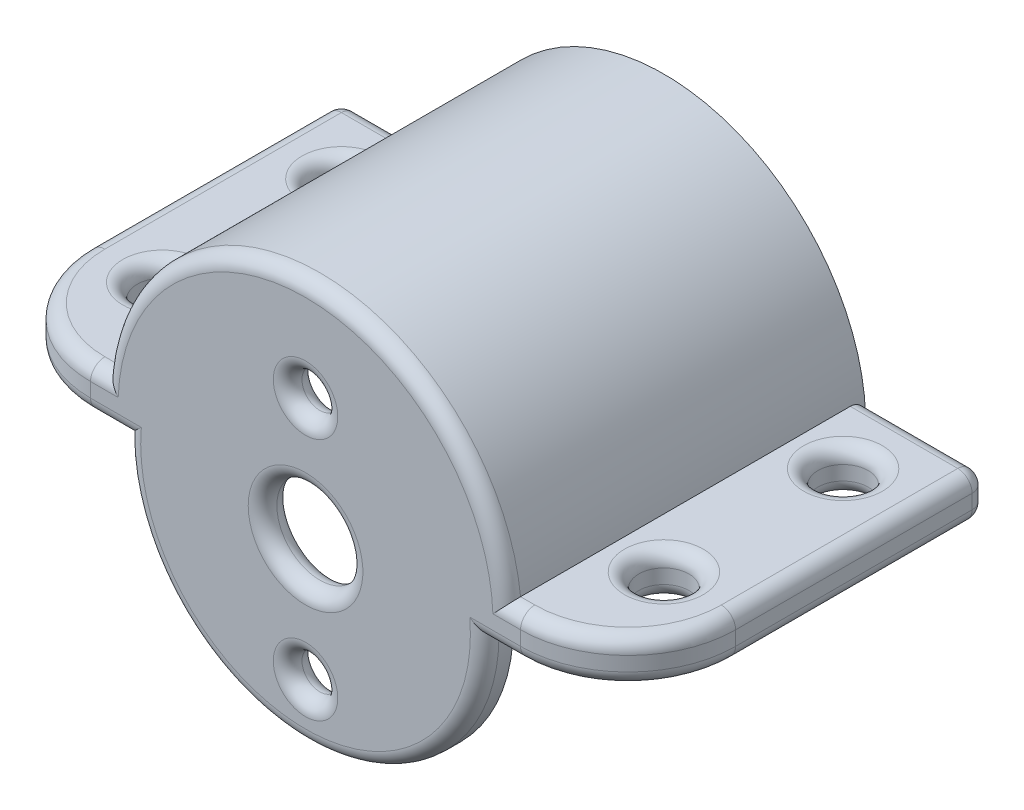
SolidWorks part; units mm, degrees
ref_plane "Front Plane" through (0, 0, 0) normal (0, 0, 1) x (1, 0, 0)
ref_plane "Top Plane" through (0, 0, 0) normal (0, 1, 0) x (1, 0, 0)
ref_plane "Right Plane" through (0, 0, 0) normal (1, 0, 0) x (0, 0, -1)
sketch "Sketch1" plane through (0, 0, 0) normal (0, 1, 0) x (1, 0, 0)
  line L1 (-22.5, 25) -> (-12.5, 25)
  line L2 (-22.5, 25) -> (-22.5, 0)
  line L3 (-22.5, 0) -> (-12.5, 0)
  line L4 (-12.5, 25) -> (-12.5, 0)
  line L5 (12.5, 25) -> (22.5, 25)
  line L6 (12.5, 25) -> (12.5, 0)
  line L7 (12.5, 0) -> (22.5, 0)
  line L8 (22.5, 25) -> (22.5, 0)
  circle A0 centre (-17.5, 20) radius 1.75
  circle A1 centre (-17.5, 7.5) radius 1.75
  circle A2 centre (17.5, 20) radius 1.75
  circle A3 centre (17.5, 7.5) radius 1.75
  point P22 (-17.5, 0)
  point P24 (17.5, 0)
  dimension "D5" = 3.5
  dimension "D1" = 25
  dimension "D2" = 12.5
  dimension "D3" = 10
  dimension "D4" = 25
  dimension "D6" = 7.5
  dimension "D7" = 5
extrude "Boss-Extrude1" add sketch "Sketch1" along normal blind 3
sketch "Sketch2" plane through (0, 0, 0) normal (0, 0, 1) x (1, 0, 0)
  line L0 (-22.5, 0) -> (-12.5, 0) construction
  line L1 (12.5, 0) -> (22.5, 0) construction
  line L2 (-14, 0) -> (-12.5, 0)
  line L3 (12.5, 0) -> (14, 0)
  arc A0 (-12.5, 0) -> (12.5, 0) centre (0, 0) cw
  arc A1 (-14, 0) -> (14, 0) centre (0, 1.5) cw
  dimension "D1" = 12.5
  dimension "D4" = 1.5
  dimension "D2" = 1.5
  dimension "D3" = 1.5
extrude "Boss-Extrude2" add sketch "Sketch2" against normal up to surface (25 mm away) up to face at (-17.5, 1.5, -25)
sketch "Sketch3" plane through (0, 0, 0) normal (0, 0, 1) x (1, 0, 0)
  arc A0 (12.5, 0) -> (-12.5, 0) centre (0, 0) ccw construction
  arc A1 (12.5, 0) -> (-12.5, 0) centre (0, 0) ccw
  circle A2 centre (0, 0) radius 12.5
  circle A3 centre (0, 8.5) radius 1.25
  circle A4 centre (0, -8.5) radius 1.25
  circle A5 centre (0, 0) radius 3
  arc M9 (-12.5, 0) -> (12.5, 0) centre (0, 0) cw
  dimension "D1" = 2.5
  dimension "D4" = 6
  dimension "D2" = 8.5
  dimension "D3" = 8.5
extrude "Boss-Extrude3" add sketch "Sketch3" against normal blind 2 contours A2 A4 A3 M9 region at (0, -12.1464, 0)
fillet "Fillet1" radius 7.5 2 edges at (-22.5, 1.5, 0) (22.5, 1.5, 0)
fillet "Fillet2" radius 1 30 edges at (22.5, 3, -16.25) (20.3033, 3, -2.1967) (22.5, 0, -16.25) (20.3033, 0, -2.1967) (-22.5, 0, -16.25) (-20.3033, 0, -2.1967) (-22.5, 3, -16.25) (-20.3033, 3, -2.1967) (1.25, 8.5, 0) (1.25, -8.5, 0) (3, 0, 0) (0, 15.5801, 0) (14.5, 3, 0) (13.75, 0, 0) (0, -12.5, 0) (-13.75, 0, 0) (-14.5, 3, 0) (-17.5, 0, -18.25) (-17.5, 3, -18.25) (-17.5, 0, -5.75) (-17.5, 3, -5.75) (17.5, 0, -18.25) (17.5, 3, -18.25) (17.5, 0, -5.75) (17.5, 3, -5.75) (1.25, -8.5, -2) (3, 0, -2) (1.25, 8.5, -2) (-12.5, 0, -13.5) (12.5, 0, -13.5)
fillet "Fillet3" radius 1 13 edges at (17.75, 3, -25) (22.2071, 2.7071, -25) (22.5, 1.5, -25) (22.2071, 0.2929, -25) (17.4815, 0, -25) (12.7825, 0.2672, -25) (-17.75, 3, -25) (-22.2071, 2.7071, -25) (-22.5, 1.5, -25) (-22.2071, 0.2929, -25) (-17.4815, 0, -25) (-12.7825, 0.2672, -25) (0, 12.5, -25)
